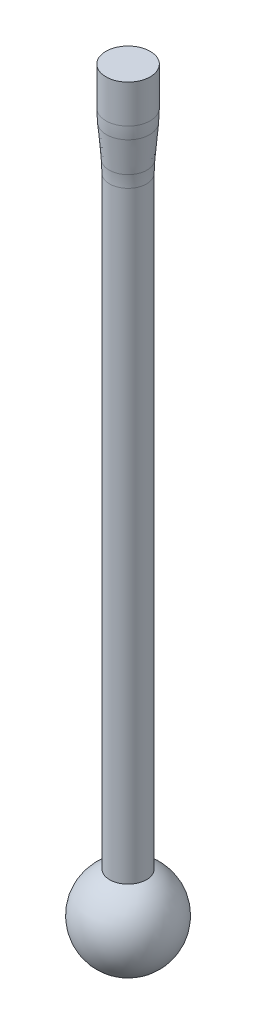
SolidWorks part; units mm, degrees
ref_plane "Front Plane" through (0, 0, 0) normal (0, 0, 1) x (1, 0, 0)
ref_plane "Top Plane" through (0, 0, 0) normal (0, 1, 0) x (1, 0, 0)
ref_plane "Right Plane" through (0, 0, 0) normal (1, 0, 0) x (0, 0, -1)
sketch "Sketch2" plane through (0, 0, 0) normal (0, 0, 1) x (1, 0, 0)
  line L0 (0, -214.1044) -> (0, 10491.1176) construction
  line L1 (0, 0) -> (1.5, 0)
  line L3 (0, 0) -> (0, -53)
  line L4 (1.25, -47.2728) -> (1.25, -6)
  line L5 (1.25, -6) -> (1.5, -3)
  line L6 (1.5, -3) -> (1.5, 0)
  arc A1 (0, -53) -> (1.25, -47.2728) centre (0, -50) ccw
  dimension "D1" = 1.25
  dimension "D4" = 6
  dimension "D2" = 3
  dimension "D3" = 50
  dimension "D5" = 3
  dimension "D6" = 6
revolve "Revolve1" add sketch "Sketch2" angle 360 about L0
fillet "Fillet1" radius 10 2 edges at (1.25, -6, 0) (1.5, -3, 0)
